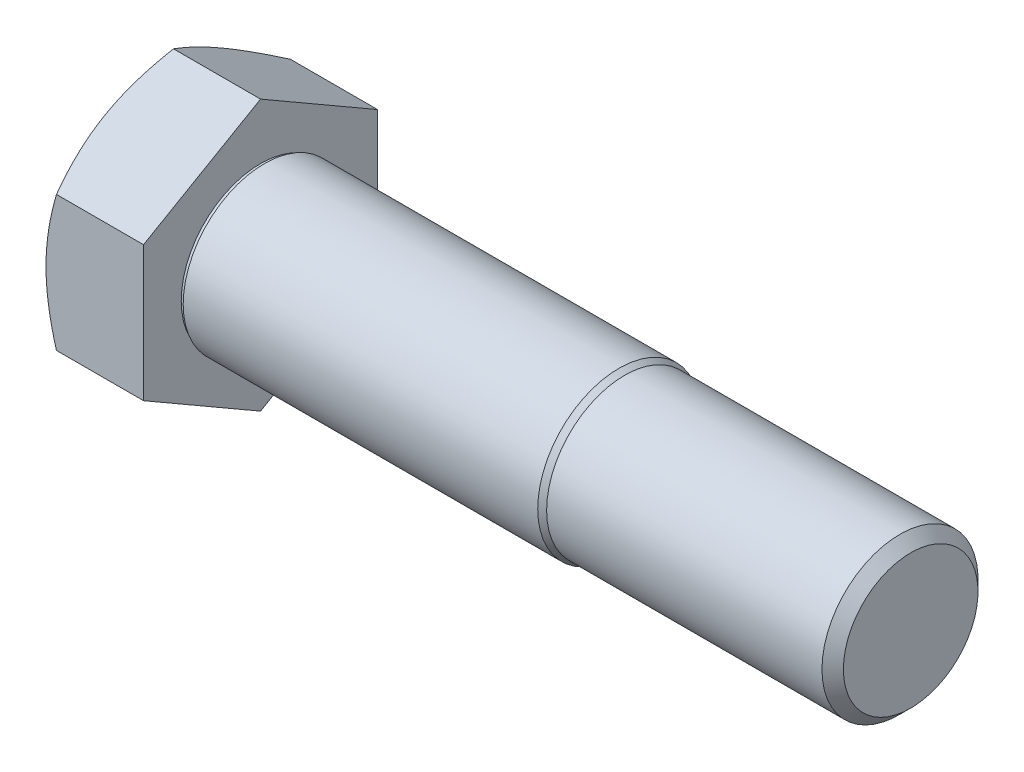
SolidWorks part; units mm, degrees
ref_plane "Front Plane" through (0, 0, 0) normal (0, 0, 1) x (1, 0, 0)
ref_plane "Top Plane" through (0, 0, 0) normal (0, 1, 0) x (1, 0, 0)
ref_plane "Right Plane" through (0, 0, 0) normal (1, 0, 0) x (0, 0, -1)
sketch "BaseHeadSke" plane through (0, 0, 0) normal (1, 0, 0) x (0, 0, -1)
  line L1 (0, 20.7846) -> (-18, 10.3923)
  line L2 (-18, 10.3923) -> (-18, -10.3923)
  line L3 (-18, -10.3923) -> (0, -20.7846)
  line L4 (0, -20.7846) -> (18, -10.3923)
  line L5 (18, -10.3923) -> (18, 10.3923)
  line L6 (18, 10.3923) -> (0, 20.7846)
  circle A0 centre (0, 0) radius 18 construction
  dimension "Width_flats" = 36
extrude "BaseHead" add sketch "BaseHeadSke" along normal blind 15
sketch "HeadChamferSke" plane through (0, 0, 0) normal (0, 0, 1) x (1, 0, 0)
  line L0 (0, 0) -> (36.4787, 0) construction
  line L1 (0, 10.3923) -> (0, -10.3923) construction
  line L2 (0, 20.7846) -> (0, 18)
  line L3 (0, 18) -> (1.6077, 20.7846)
  line L4 (1.6077, 20.7846) -> (0, 20.7846)
  line L7 (15, 20.7846) -> (0, 20.7846) construction
  dimension "Angle_Chamfer_Head" = 30
revolve "HeadChamfer" cut sketch "HeadChamferSke" angle 360 about L0
sketch "BodySke" plane through (0, 0, 0) normal (0, 0, 1) x (1, 0, 0)
  line L0 (0, 0) -> (144.9862, 0) construction
  line L1 (15, 12.2) -> (15.6, 12.2)
  line L2 (15, 10.3923) -> (15, -10.3923) construction
  line L3 (15.6, 12.2) -> (15.6, 12.5)
  line L4 (15.6, 12.5) -> (70.134, 12.5)
  line L5 (70.134, 12.5) -> (71, 12)
  line L6 (71, 12) -> (113.352, 12)
  line L7 (113.352, 12) -> (115, 10.352)
  line L8 (115, 10.352) -> (115, 0)
  line L9 (115, 0) -> (15, 0)
  line L10 (15, 0) -> (15, 12.2)
  line L11 (18, 0) -> (18, 23.2443) construction
  line L12 (78.5, 0) -> (78.5, 26.3648) construction
  dimension "D3" = 7.5
  dimension "Thread_length" = 36.5
  dimension "Thread_minor" = 20.704
  dimension "Advance" = 3
revolve "BaseBody" add sketch "BodySke" angle 360 about L0
cosmetic thread "ThreadCosmetic" [suppressed] parameters "Thread_length"=36.5, "Thread_minor"=20.704
sketch "ThdSchSke" plane through (0, 0, 0) normal (0, 0, 1) x (1, 0, 0)
  line L0 (0, 0) -> (125.7008, 0) construction
  line L1 (110.352, 13.9029) -> (110.352, 12)
  line L2 (110.352, 13.9029) -> (112.2549, 13.9029)
  line L3 (112.2549, 13.9029) -> (112.2549, 12)
  line L4 (112.2549, 12) -> (111.3035, 10.352)
  line L5 (111.3035, 10.352) -> (110.352, 12)
  dimension "D1" = 3
revolve "ThreadSchematic" [suppressed] cut sketch "ThdSchSke" angle 360 about L0
pattern_linear "ThdSchPat" [suppressed] of bodies 116
equation "\"D3@BodySke\" = \"Advance@BodySke\" * 2.5"
equation "\"Thread_length@ThreadCosmetic\" = \"Thread_length@BodySke\""
equation "\"Thread_minor@ThreadCosmetic\" = \"Thread_minor@BodySke\""
equation "\"D1@ThdSchSke\" = \"Advance@BodySke\""
equation "\"Tooth_Num@ThdSchPat\" =  int( \"Thread_length@BodySke\" / \"Advance@BodySke\" ) - 1 "
equation "\"Advance@ThdSchPat\" = \"Advance@BodySke\""
